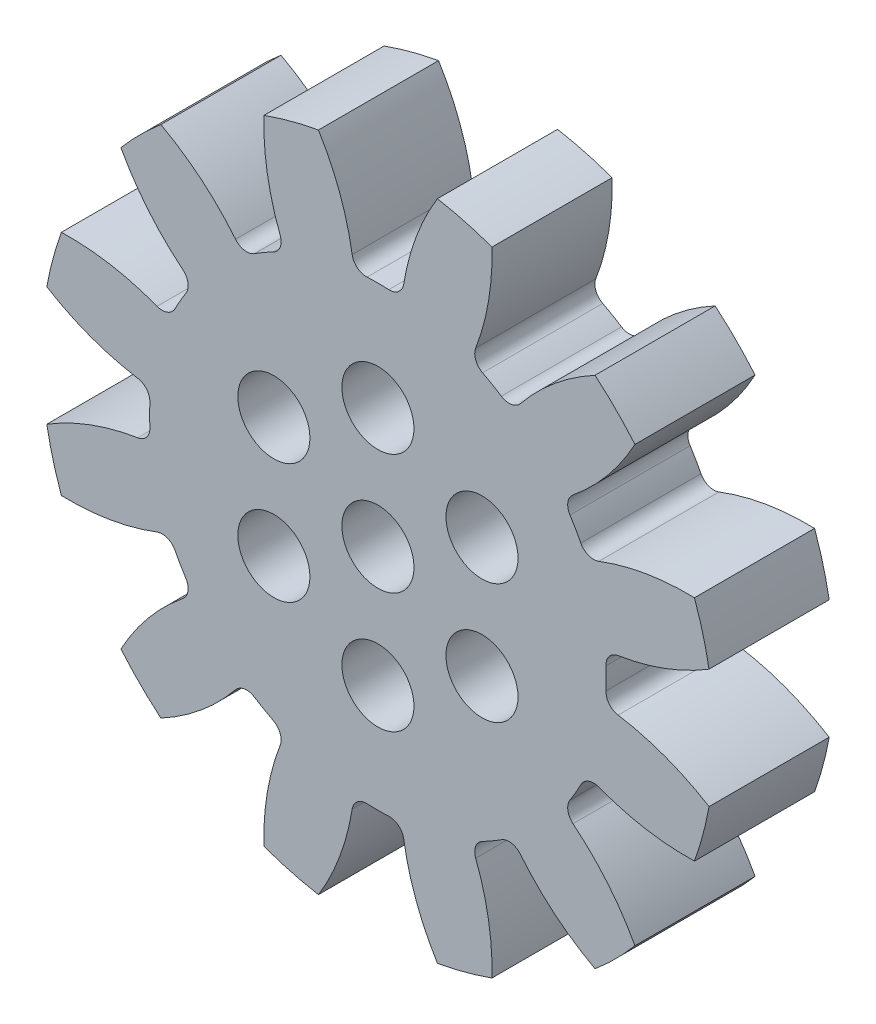
SolidWorks part; units mm, degrees
ref_plane "Front Plane" through (0, 0, 0) normal (0, 0, 1) x (1, 0, 0)
ref_plane "Top Plane" through (0, 0, 0) normal (0, 1, 0) x (1, 0, 0)
ref_plane "Right Plane" through (0, 0, 0) normal (1, 0, 0) x (0, 0, -1)
sketch "Sketch1" plane through (0, 0, 0) normal (0, 0, 1) x (1, 0, 0)
  circle A0 centre (0, 0) radius 12
  circle A1 centre (0, 0) radius 9.5
  circle A2 centre (0, 0) radius 14
  dimension "D1" = 24
  dimension "D2" = 28
  dimension "D3" = 4.5
extrude "Boss-Extrude1" add sketch "Sketch1" along normal mid plane 5 contours A2
sketch "Sketch2" plane through (0, 0, 0) normal (0, 0, 1) x (1, 0, 0)
  line L0 (0, 0) -> (0, 14) construction
  line L1 (-0.9997, 9.4472) -> (0, 0) construction
  line L2 (-1.5663, 11.8973) -> (1.5663, 11.8973) construction
  line L3 (0, 7.5939) -> (-2.7213, 15.0705) construction
  line L4 (0, 0) -> (3.6235, 13.523) construction
  line L5 (1.5663, 11.8973) -> (4.5922, 11.0866) construction
  circle A0 centre (0, 0) radius 14 construction
  arc A1 (-3.3146, 14.9512) -> (-0.9997, 9.4472) centre (-11.2897, 8.3583) cw
  arc A2 (3.3146, 14.9512) -> (0.9997, 9.4472) centre (11.2897, 8.3583) ccw
  arc A3 (3.3146, 14.9512) -> (-3.3146, 14.9512) centre (0, 0) ccw
  arc A4 (0.9997, 9.4472) -> (-0.9997, 9.4472) centre (0, 0) ccw
  circle A6 centre (0, 0) radius 9.5 construction
  circle A7 centre (0, 0) radius 12 construction
  dimension "D1" = 20
  dimension "D2" = 15
extrude "Cut-Extrude1" cut sketch "Sketch2" against normal through all both and the other way through all
fillet "Fillet1" radius 0.6 1 edges at (-0.9997, 9.4472, 0) type face fillet first side face at (-1.6166, 11.6546, 0) second side face at (0, 9.4736, 0)
fillet "Fillet2" radius 0.6 1 edges at (0.9997, 9.4472, 0) type face fillet first side face at (1.6166, 11.6546, 0) second side face at (0.2746, 9.4821, 0)
sketch "Sketch3" plane through (0, 0, 2.5) normal (0, 0, 1) x (1, 0, 0)
pattern_circular "CirPattern2" count 12 over 360 about axis through (0, 0, 2.5) along (0, 0, 1) of "Fillet1", "Cut-Extrude1", "Fillet2"
sketch "Sketch4" plane through (0, 0, 2.5) normal (0, 0, 1) x (1, 0, 0)
  line L0 (0, 0) -> (0, 8.1574) construction
  circle A0 centre (0, 0) radius 1.5
  circle A1 centre (0, 5) radius 1.5
  circle A2 centre (4.3301, 2.5) radius 1.5
  circle A3 centre (4.3301, -2.5) radius 1.5
  circle A4 centre (0, -5) radius 1.5
  circle A5 centre (-4.3301, -2.5) radius 1.5
  circle A6 centre (-4.3301, 2.5) radius 1.5
  point P18 (0, 0)
  dimension "D1" = 3
  dimension "D2" = 3
  dimension "D3" = 5
  dimension "D4" = 6
extrude "Cut-Extrude2" cut sketch "Sketch4" against normal through all both and the other way through all
equation "\"Number of Teeth\"= 12"
equation "\"Module\"= 2mm"
equation "\"D2@Sketch2\"=180 / \"Number of Teeth\""
equation "\"D1@Sketch1\"= \"Module\" * \"Number of Teeth\""
equation "\"D2@Sketch1\"=(\"Number of Teeth\" + 2) * \"Module\""
equation "\"D3@Sketch1\"= \"Module\" * 2.25"
equation "\"D1@CirPattern2\"= \"Number of Teeth\""
